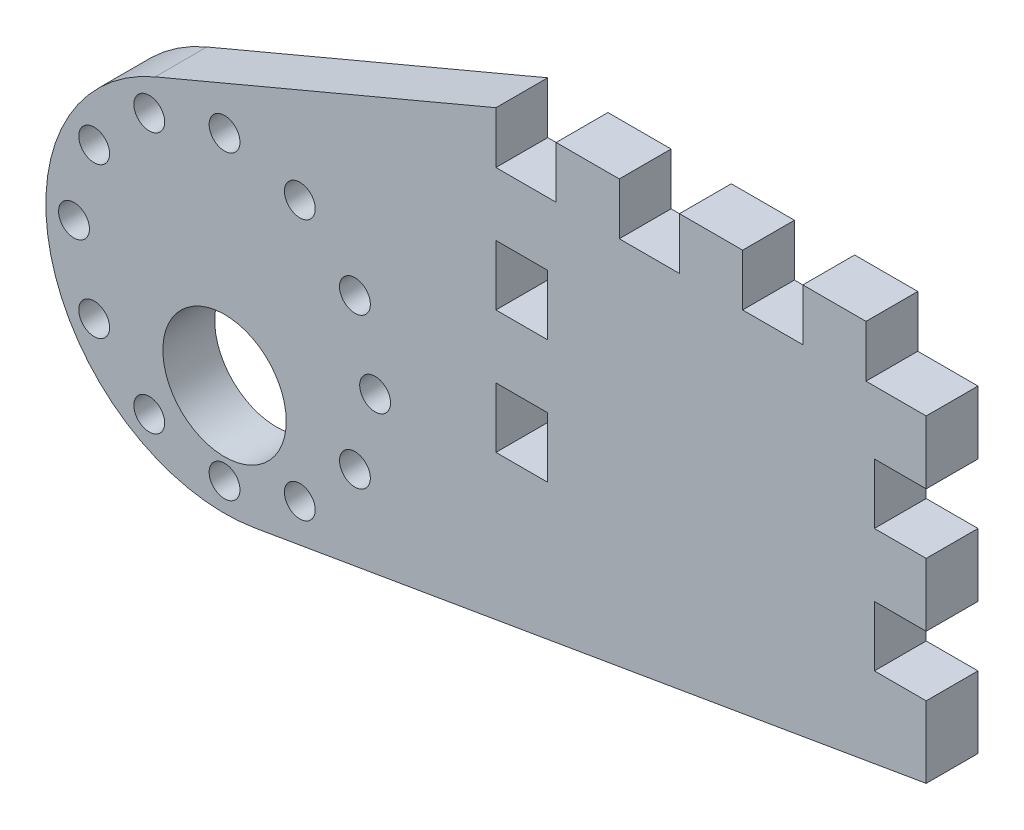
SolidWorks part; units mm, degrees
material "Teak"
ref_plane "Front Plane" through (0, 0, 0) normal (0, 0, 1) x (1, 0, 0)
ref_plane "Top Plane" through (0, 0, 0) normal (0, 1, 0) x (1, 0, 0)
ref_plane "Right Plane" through (0, 0, 0) normal (1, 0, 0) x (0, 0, -1)
sketch "Sketch1" plane through (0, 0, 0) normal (0, 0, 1) x (1, 0, 0)
  line L0 (27.94, 31.75) -> (72.2376, 31.75)
  line L1 (34.29, 31.75) -> (245.11, 31.75) construction
  line L2 (72.2376, 31.75) -> (72.2376, -6.35)
  line L3 (72.2376, -6.35) -> (3.0923, -18.1383)
  line L4 (27.94, 31.75) -> (-7.149, 16.9544)
  circle A0 centre (0, 0) radius 18.4 construction
  circle A1 centre (0, 0) radius 18.4
  circle A2 centre (0, -7) radius 6 construction
  circle A3 centre (0, -7) radius 6 construction
  circle A4 centre (0, -7) radius 6.35
  point P6 (0, 15.5)
  point P7 (7.75, 13.4234)
  point P9 (13.4234, 7.75)
  point P11 (15.5, 0)
  point P13 (13.4234, -7.75)
  point P15 (7.75, -13.4234)
  point P17 (0, -15.5)
  point P19 (-7.75, -13.4234)
  point P21 (-13.4234, -7.75)
  point P23 (-15.5, 0)
  point P25 (-13.4234, 7.75)
  point P27 (-7.75, 13.4234)
  point P29 (-44.2035, 6.0317)
  dimension "D3" = 12.7
  dimension "D1" = 38.1
  dimension "D2" = 44.2976
extrude "Boss-Extrude1" add sketch "Sketch1" along normal blind 5.334 contours A1 L3 L2 L0 L4 | A1 region at (41.6997, 10.3028, 0)
extrude "Cut-Extrude2" cut sketch "Sketch1<3>" along normal through all contours A4 region at (0, -7, 0)
sketch "Sketch1<3>" plane through (0, 0, 0) normal (0, 0, 1) x (1, 0, 0) same geometry as "Sketch1"
hole_wizard "1/8 (0.125) Diameter Hole1" positions "Sketch3" profile "Sketch2" hole size "1/8" standard "ANSI Inch" end condition through all
sketch "Sketch3" plane through (0, 0, 5.334) normal (0, 0, 1) x (1, 0, 0)
  point P0 (0, 15.5)
  point P3 (7.75, 13.4234)
  point P6 (13.4234, 7.75)
  point P9 (15.5, 0)
  point P12 (13.4234, -7.75)
  point P15 (7.75, -13.4234)
  point P18 (0, -15.5)
  point P21 (-7.75, -13.4234)
  point P24 (-13.4234, -7.75)
  point P27 (-15.5, 0)
  point P30 (-13.4234, 7.75)
  point P33 (-7.75, 13.4234)
sketch "Sketch2" plane through (0, 15.5, 5.334) normal (1, 0, 0) x (0, -1, 0)
  line L0 (0, 0) -> (0, 5.334)
  line L1 (0, 5.334) -> (1.5875, 5.334)
  line L2 (1.5875, 5.334) -> (1.5875, 0)
  line L5 (1.5875, 0) -> (0, 0)
  line L11 (0, -6.35) -> (0, 107.95) construction
  dimension "Thru Hole Dia." = 3.175
  dimension "Thru Hole Depth" = 5.334
sketch "Sketch4" plane through (0, 0, 5.334) normal (0, 0, 1) x (1, 0, 0)
  line L1 (27.94, 31.75) -> (34.1376, 31.75)
  line L2 (27.94, 31.75) -> (27.94, 26.416)
  line L3 (27.94, 26.416) -> (34.1376, 26.416)
  line L4 (34.1376, 31.75) -> (34.1376, 26.416)
  dimension "D1" = 6.1976
  dimension "D2" = 5.334
extrude "Cut-Extrude3" cut sketch "Sketch4" against normal through all
pattern_linear "LPattern1" count 4 spacing 12.7 along (1, 0, 0) of "Cut-Extrude3"
sketch "Sketch5" plane through (0, 0, 5.334) normal (0, 0, 1) x (1, 0, 0)
  line L0 (72.2376, 26.416) -> (72.2376, -6.35) construction
  line L1 (72.2376, 19.9136) -> (66.9036, 19.9136)
  line L2 (72.2376, 19.9136) -> (72.2376, 13.716)
  line L3 (72.2376, 13.716) -> (66.9036, 13.716)
  line L4 (66.9036, 19.9136) -> (66.9036, 13.716)
  line L5 (66.04, 26.416) -> (72.2376, 26.416) construction
  line L6 (27.94, 31.75) -> (27.94, 26.416) construction
  line L7 (33.274, 19.9136) -> (27.94, 19.9136)
  line L8 (33.274, 19.9136) -> (33.274, 13.716)
  line L9 (33.274, 13.716) -> (27.94, 13.716)
  line L10 (27.94, 19.9136) -> (27.94, 13.716)
  dimension "D1" = 6.5024
  dimension "D2" = 5.334
  dimension "D3" = 6.1976
extrude "Cut-Extrude4" cut sketch "Sketch5" against normal through all
pattern_linear "LPattern2" count 2 spacing 12.7 along (0, -1, 0) of "Cut-Extrude4"
